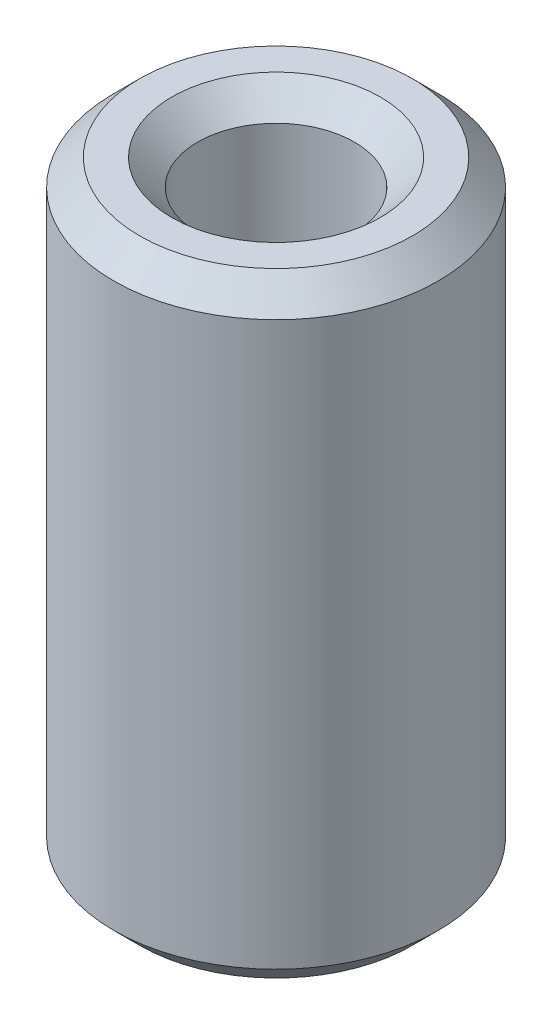
SolidWorks part; units mm, degrees
ref_plane "Front Plane" through (0, 0, 0) normal (0, 0, 1) x (1, 0, 0)
ref_plane "Top Plane" through (0, 0, 0) normal (0, 1, 0) x (1, 0, 0)
ref_plane "Right Plane" through (0, 0, 0) normal (1, 0, 0) x (0, 0, -1)
sketch "Sketch1" plane through (0, 0, 0) normal (0, 1, 0) x (1, 0, 0)
  circle A0 centre (0, 0) radius 10
  dimension "SLEEVE_OD" = 20
extrude "Boss-Extrude1" add sketch "Sketch1" along normal blind 37.8666
sketch "Sketch2" plane through (0, 0, 0) normal (0, 1, 0) x (1, 0, 0)
  circle A0 centre (0, 0) radius 4.8319
  dimension "BORE_D" = 9.6638
extrude "Cut-Extrude1" cut sketch "Sketch2" along normal through all
chamfer "Chamfer1" distance 1.6011 angle 45 4 edges at (0, 37.8666, 4.8319) (0, 0, 4.8319) (0, 0, 10) (0, 37.8666, 10)
